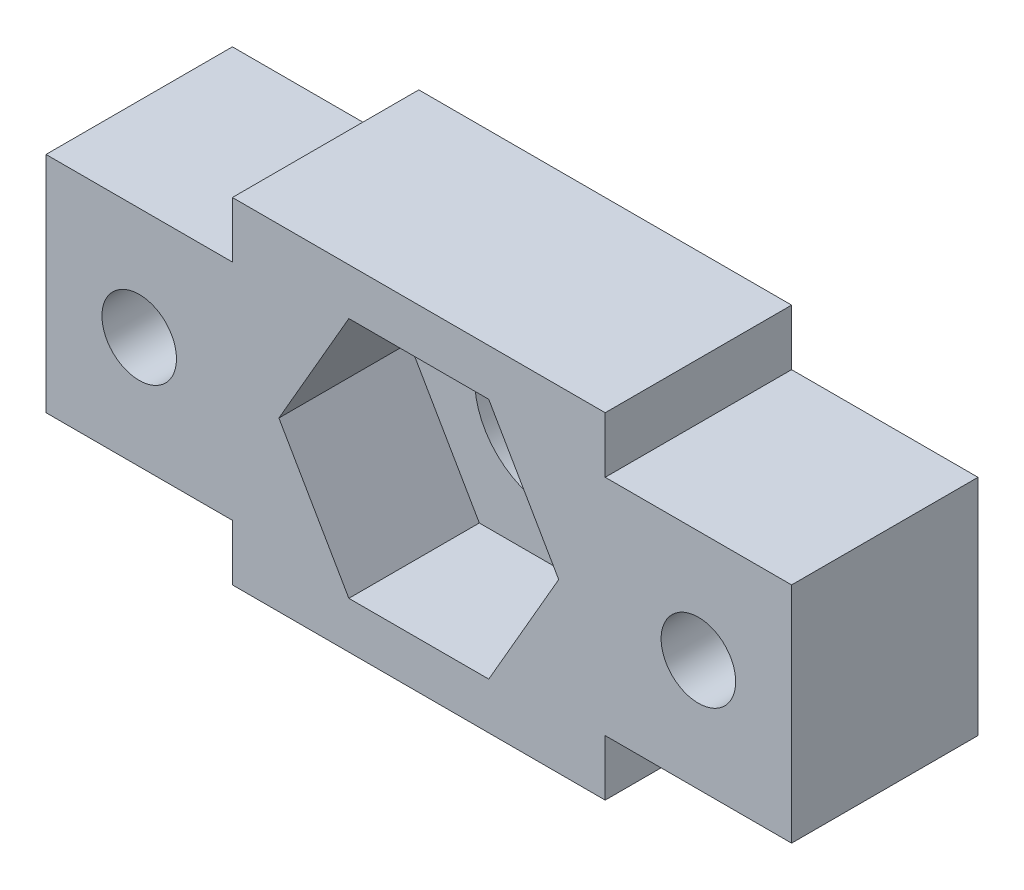
SolidWorks part; units mm, degrees
note: The reader was unsure of these and kept them because the rebuilt part matched: shared geometry of "Sketch2<4>", "Sketch3<4>".
material "ABS"
ref_plane "Front Plane" through (0, 0, 0) normal (0, 0, 1) x (1, 0, 0)
ref_plane "Top Plane" through (0, 0, 0) normal (0, 1, 0) x (1, 0, 0)
ref_plane "Right Plane" through (0, 0, 0) normal (1, 0, 0) x (0, 0, -1)
sketch "Sketch1" plane through (0, 0, 0) normal (0, 0, 1) x (1, 0, 0)
  line L1 (-40, -19) -> (-80, -19)
  line L2 (-40, -19) -> (-40, -31)
  line L3 (-40, -31) -> (-80, -31)
  line L4 (-80, -19) -> (-80, -31)
  line L5 (-40, -19) -> (-80, -31) construction
  line L6 (-40, -31) -> (-80, -19) construction
  circle A0 centre (-45, -25) radius 2
  circle A1 centre (-75, -25) radius 2
  circle A2 centre (-60, -25) radius 4
  point P13 (-60, -25)
  dimension "D1" = 8
  dimension "D2" = 4
  dimension "D3" = 4
  dimension "D4" = 6
  dimension "D5" = 6
  dimension "D6" = 5
  dimension "D7" = 5
extrude "Boss-Extrude1" add sketch "Sketch1" along normal blind 3
sketch "Sketch2" plane through (0, 0, 3) normal (0, 0, 1) x (1, 0, 0)
  line L0 (-40, -19) -> (-80, -19) construction
  line L1 (-56.2472, -18.5) -> (-63.7528, -18.5)
  line L2 (-63.7528, -18.5) -> (-67.5056, -25)
  line L3 (-67.5056, -25) -> (-63.7528, -31.5)
  line L4 (-63.7528, -31.5) -> (-56.2472, -31.5)
  line L5 (-56.2472, -31.5) -> (-52.4944, -25)
  line L6 (-52.4944, -25) -> (-56.2472, -18.5)
  line L7 (-50, -16) -> (-50, -34)
  line L8 (-50, -16) -> (-70, -16)
  line L9 (-50, -34) -> (-70, -34)
  line L10 (-70, -16) -> (-70, -34)
  circle A0 centre (-60, -25) radius 6.5 construction
  dimension "D1" = 13
  dimension "D2" = 9
  dimension "D3" = 9
  dimension "D4" = 10
  dimension "D5" = 10
extrude "Boss-Extrude2" add sketch "Sketch2" along normal blind 7
extrude "Boss-Extrude3" add sketch "Sketch2<4>" against normal up to surface (3 mm away)
sketch "Sketch2<4>" plane through (0, 0, 3) normal (0, 0, 1) x (1, 0, 0) same geometry as "Sketch2"
sketch "Sketch3" plane through (0, 0, 3) normal (0, 0, 1) x (1, 0, 0)
  line L0 (-80, -19) -> (-40, -19)
  line L1 (-80, -19) -> (-80, -31)
  line L2 (-40, -19) -> (-40, -31)
  line L3 (-80, -31) -> (-40, -31)
  line L4 (-50, -16) -> (-70, -16) construction
  line L5 (-70, -34) -> (-50, -34)
  line L6 (-70, -34) -> (-70, -16)
  line L7 (-70, -16) -> (-50, -16)
  line L8 (-50, -34) -> (-50, -16)
  line L9 (-70, -34) -> (-50, -16) construction
  line L10 (-70, -16) -> (-50, -34) construction
  line L11 (-70, -16) -> (-70, -34) construction
  line L12 (-70, -34) -> (-50, -34) construction
  line L13 (-80, -31) -> (-70, -31) construction
  line L14 (-50, -34) -> (-50, -16) construction
  line L15 (-67.5056, -25) -> (-63.7528, -31.5) construction
  line L16 (-52.4944, -25) -> (-56.2472, -18.5)
  line L17 (-56.2472, -18.5) -> (-63.7528, -18.5)
  line L18 (-63.7528, -18.5) -> (-67.5056, -25)
  line L19 (-67.5056, -25) -> (-63.7528, -31.5)
  line L20 (-63.7528, -31.5) -> (-56.2472, -31.5)
  line L21 (-56.2472, -31.5) -> (-52.4944, -25)
  circle A0 centre (-60, -25) radius 6.5 construction
  circle A1 centre (-75, -25) radius 2
  circle A2 centre (-45, -25) radius 2
  point P10 (-60, -25)
  circle M7 centre (-75, -25) radius 2
  line M8 (-70, -31) -> (-70, -19)
  line M9 (-70, -19) -> (-80, -19)
  line M10 (-80, -19) -> (-80, -31)
  line M11 (-80, -31) -> (-70, -31)
extrude "Boss-Extrude4" add sketch "Sketch3" against normal up to surface (10 mm away) from surface contours L21 L3 L8 L0 L16 | L21 L20 L19 L3 L6 L5 L8 | L19 L18 L0 L3 M8 | L18 L17 L16 L0 L8 L7 L6 | M11 M8 M9 M10 M7 | L8 L3 L2 L0 A2
extrude "Boss-Extrude5" add sketch "Sketch3<4>" against normal up to surface (3 mm away) contours L17 L18 L0 L16 | L20 L21 L3 L19 up to face at (-60, -31.25, 0)
sketch "Sketch3<4>" plane through (0, 0, 3) normal (0, 0, 1) x (1, 0, 0) same geometry as "Sketch3"
